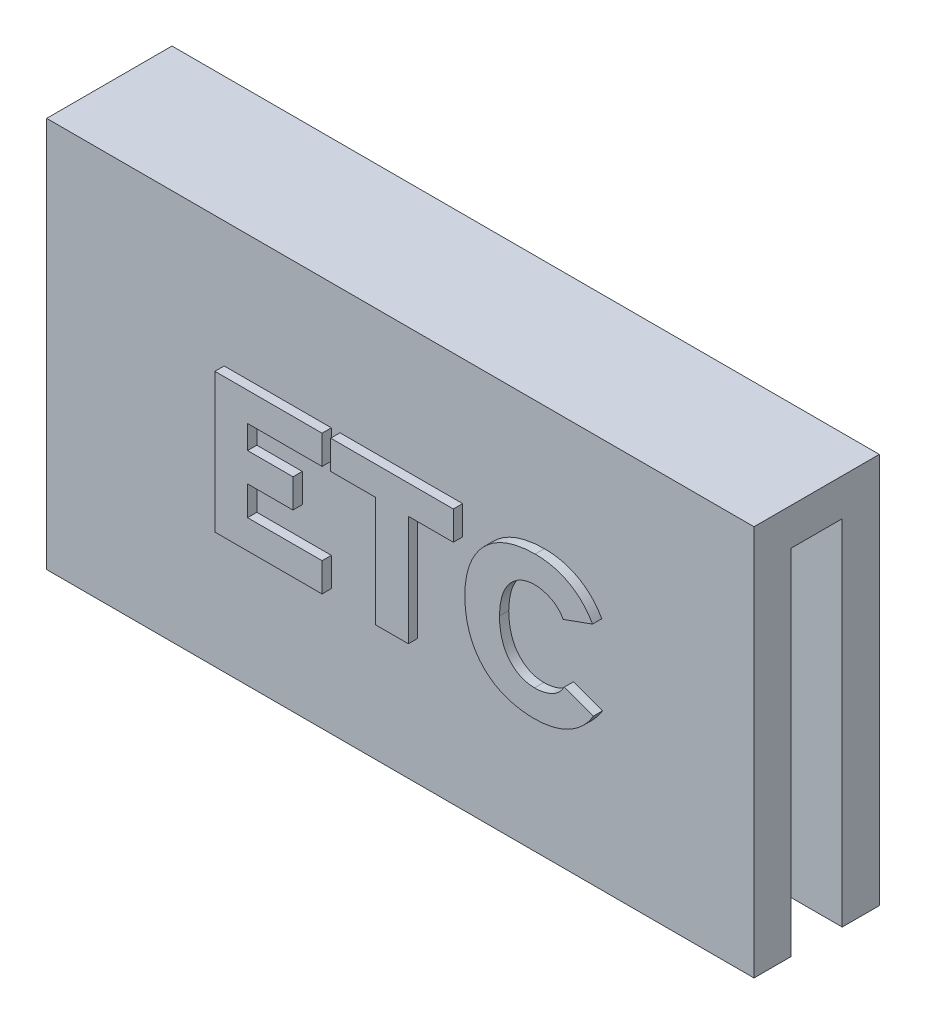
SolidWorks part; units mm, degrees
ref_plane "Front Plane" through (0, 0, 0) normal (0, 0, 1) x (1, 0, 0)
ref_plane "Top Plane" through (0, 0, 0) normal (0, 1, 0) x (1, 0, 0)
ref_plane "Right Plane" through (0, 0, 0) normal (1, 0, 0) x (0, 0, -1)
sketch "Sketch1" plane through (0, 0, 0) normal (1, 0, 0) x (0, 0, -1)
  line L0 (0, 0) -> (0, 42.1)
  line L1 (0, 42.1) -> (13.5, 42.1)
  line L2 (13.5, 42.1) -> (13.5, 0)
  line L3 (13.5, 0) -> (9.5, 0)
  line L4 (9.5, 0) -> (9.5, 38.1)
  line L5 (9.5, 38.1) -> (4, 38.1)
  line L6 (4, 38.1) -> (4, 0)
  line L7 (4, 0) -> (0, 0)
  line L8 (4, 38.1) -> (4, 42.1) construction
  dimension "D1" = 38.1
  dimension "D2" = 4
  dimension "D3" = 5.5
extrude "Boss-Extrude1" add sketch "Sketch1" along normal mid plane 76.2 contours L1 L2 L3 L4 L5 L6 L7 L0
sketch "Sketch2" plane through (0, 0, 0) normal (0, 0, 1) x (1, 0, 0)
  line L0 (-38.1, 13.55) -> (38.1, 13.55) construction
  line L1 (-38.1, 0) -> (-38.1, 42.1) construction
  line L2 (38.1, 0) -> (38.1, 42.1) construction
  line L3 (-38.1, 21.05) -> (49961.9, 21.05) construction
  line L4 (-38.1, 28.55) -> (38.1, 28.55) construction
  line L5 (-38.1, 28.55) -> (-38.1, 13.55) construction
  text T0 "<b>ETC</b>" font "Atkinson Hyperlegible" height 15
  point P9 (-38.1, 21.05)
  point P12 (-38.1, 21.05)
  dimension "D1" = 15
extrude "Boss-Extrude3" add sketch "Sketch2" along normal mid plane 2
